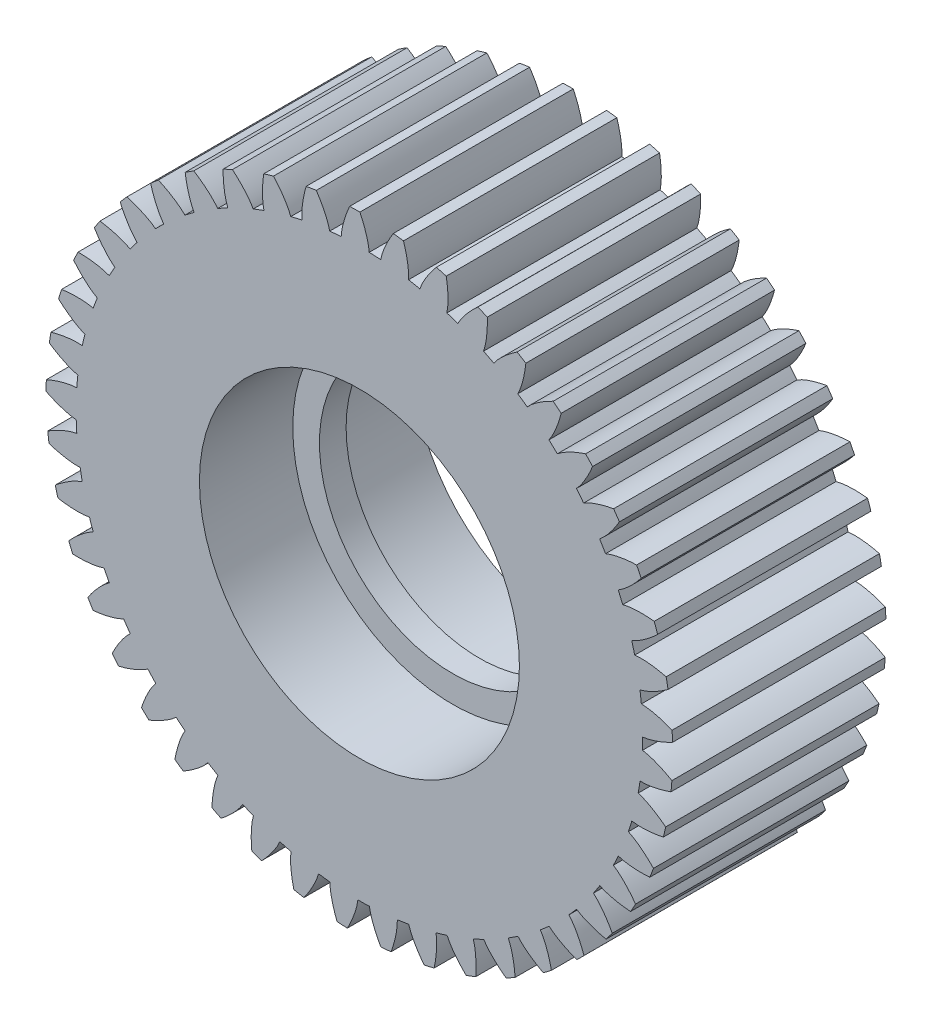
SolidWorks part; units mm, degrees
material "ABS"
ref_plane "Front Plane" through (0, 0, 0) normal (0, 0, 1) x (1, 0, 0)
ref_plane "Top Plane" through (0, 0, 0) normal (0, 1, 0) x (1, 0, 0)
ref_plane "Right Plane" through (0, 0, 0) normal (1, 0, 0) x (0, 0, -1)
sketch "Sketch1" plane through (0, 0, 0) normal (0, 0, 1) x (1, 0, 0)
  circle A0 centre (0, 0) radius 11.75
  dimension "D1" = 23.5
extrude "Boss-Extrude1" add sketch "Sketch1" along normal mid plane 8
sketch "Sketch2" plane through (0, 0, 0) normal (0, 0, 1) x (1, 0, 0)
  line L0 (0, 0) -> (10.5715, 0) construction
  line L1 (0, 0) -> (11.2477, -0.225) construction
  line L2 (0, 0) -> (10.5631, -0.4228) construction
  line L3 (10.5715, 0) -> (10.625, 0)
  line L4 (10.5631, -0.4228) -> (10.6165, -0.4249)
  circle A0 centre (0, 0) radius 11.25 construction
  circle A1 centre (0, 0) radius 10.5715 construction
  circle A2 centre (0, 0) radius 10.625
  circle A3 centre (0, 0) radius 11.75 construction
  circle A4 centre (0, 0) radius 11.75
  spline S0 degree 4 poles (10.5715, 0) (10.5752, 0.0001) (10.5853, 0.0004) (10.6044, 0.0016) (10.6356, 0.0045) (10.6753, 0.0095) (10.7265, 0.0174) (10.7865, 0.0288) (10.8523, 0.0433) (10.9236, 0.0613) (10.9945, 0.0812) (11.0648, 0.1028) (11.1346, 0.126) (11.2188, 0.1559) (11.3192, 0.1944) (11.4357, 0.2433) (11.5668, 0.3032) (11.6991, 0.369) (11.8282, 0.4376) (11.9573, 0.5114) (12.0813, 0.5859) (12.2085, 0.6678) (12.3252, 0.7457) (12.4542, 0.8378) (12.5578, 0.9136) (12.6924, 1.0187) (12.7713, 1.0823) (12.8629, 1.1585) (12.9032, 1.1933) (12.9281, 1.2147) knots 0 0 0 0 0 0.005377 0.015084 0.028532 0.04661 0.064855 0.092111 0.119476 0.146842 0.174209 0.201575 0.228941 0.256307 0.307035 0.361767 0.4165 0.471232 0.525964 0.580697 0.635429 0.690161 0.744894 0.799626 0.854358 0.909091 0.954545 1 1 1 1 1 construction
  spline S1 degree 4 poles (10.5715, 0) (10.5752, 0.0001) (10.5853, 0.0004) (10.6044, 0.0016) (10.6356, 0.0045) (10.6753, 0.0095) (10.7265, 0.0174) (10.7865, 0.0288) (10.8523, 0.0433) (10.9236, 0.0613) (10.9945, 0.0812) (11.0648, 0.1028) (11.1346, 0.126) (11.2188, 0.1559) (11.3192, 0.1944) (11.4357, 0.2433) (11.5668, 0.3032) (11.6991, 0.369) (11.8282, 0.4376) (11.9573, 0.5114) (12.0813, 0.5859) (12.2085, 0.6678) (12.3252, 0.7457) (12.4542, 0.8378) (12.5578, 0.9136) (12.6632, 0.9959) (12.7143, 1.0366) (12.7403, 1.0576) knots 0 0 0 0 0 0.005377 0.015084 0.028532 0.04661 0.064855 0.092111 0.119476 0.146842 0.174209 0.201575 0.228941 0.256307 0.307035 0.361767 0.4165 0.471232 0.525964 0.580697 0.635429 0.690161 0.744894 0.799626 0.854358 0.909091 0.909091 0.909091 0.909091 0.909091
  spline S2 degree 4 poles (10.5631, -0.4228) (10.5667, -0.423) (10.5768, -0.4237) (10.5959, -0.4257) (10.6269, -0.4298) (10.6664, -0.4364) (10.7172, -0.4464) (10.7768, -0.4602) (10.8419, -0.4773) (10.9124, -0.4981) (10.9824, -0.5208) (11.0518, -0.5452) (11.1207, -0.5712) (11.2036, -0.6045) (11.3024, -0.647) (11.4168, -0.7005) (11.5454, -0.7655) (11.675, -0.8366) (11.8012, -0.9103) (11.9273, -0.9892) (12.0482, -1.0686) (12.1721, -1.1555) (12.2856, -1.238) (12.4108, -1.3352) (12.5112, -1.4151) (12.6415, -1.5255) (12.7178, -1.5922) (12.8063, -1.672) (12.8452, -1.7084) (12.8691, -1.7308) knots 0 0 0 0 0 0.005377 0.015084 0.028532 0.04661 0.064855 0.092111 0.119476 0.146842 0.174209 0.201575 0.228941 0.256307 0.307035 0.361767 0.4165 0.471232 0.525964 0.580697 0.635429 0.690161 0.744894 0.799626 0.854358 0.909091 0.954545 1 1 1 1 1 construction
  spline S3 degree 4 poles (10.5631, -0.4228) (10.5667, -0.423) (10.5768, -0.4237) (10.5959, -0.4257) (10.6269, -0.4298) (10.6664, -0.4364) (10.7172, -0.4464) (10.7768, -0.4602) (10.8419, -0.4773) (10.9124, -0.4981) (10.9824, -0.5208) (11.0518, -0.5452) (11.1207, -0.5712) (11.2036, -0.6045) (11.3024, -0.647) (11.4168, -0.7005) (11.5454, -0.7655) (11.675, -0.8366) (11.8012, -0.9103) (11.9273, -0.9892) (12.0482, -1.0686) (12.1721, -1.1555) (12.2856, -1.238) (12.4108, -1.3352) (12.5112, -1.4151) (12.6133, -1.5016) (12.6627, -1.5442) (12.6878, -1.5663) knots 0 0 0 0 0 0.005377 0.015084 0.028532 0.04661 0.064855 0.092111 0.119476 0.146842 0.174209 0.201575 0.228941 0.256307 0.307035 0.361767 0.4165 0.471232 0.525964 0.580697 0.635429 0.690161 0.744894 0.799626 0.854358 0.909091 0.909091 0.909091 0.909091 0.909091
  dimension "D1" = 22.5
  dimension "D2" = 21.1431
  dimension "D3" = 21.25
  dimension "D4" = 1.146
  dimension "D5" = 1.146
extrude "Cut-Extrude1" cut sketch "Sketch2" against normal through all both and the other way through all contours A2 S3 A4 S1 region at (11.2841, -0.2257, 0)
pattern_circular "CirPattern2" count 45 over 360 about axis through (0, 0, 4) along (0, 0, -1) of "Cut-Extrude1"
sketch "Sketch3" plane through (0, 0, 4) normal (0, 0, 1) x (1, 0, 0)
  circle A0 centre (0, 0) radius 6
  dimension "D1" = 12
extrude "Cut-Extrude2" cut sketch "Sketch3" against normal blind 3.5
sketch "Sketch4" plane through (0, 0, 0.5) normal (0, 0, 1) x (1, 0, 0)
  circle A0 centre (0, 0) radius 5
  dimension "D1" = 10
extrude "Cut-Extrude3" cut sketch "Sketch4" against normal through all
mirror "Mirror1" about plane through (0, 0, 0) normal (0, 0, 1) of "Cut-Extrude2"
equation "\"Np\" = 45"
equation "\"module\" = 0.5"
equation "\"pressure angle\" = 20.0"
equation "\"h_a\" = 0.5"
equation "\"h_b\" = 0.625"
equation "\"clr_tip_root\" = 0.125"
equation "\"dp_p\" = 22.5"
equation "\"db_p\" = 21.14308396768294"
equation "\"D1@Sketch1\"= \"dp_p\" + 2*\"h_a\" "
equation "\"fw_p\" = 8.0"
equation "\"D1@Boss-Extrude1\"=\"fw_p\""
equation "\"D1@Sketch2\"=\"dp_p\""
equation "\"D2@Sketch2\"= \"db_p\""
equation "\"D3@Sketch2\"=\"dp_p\"- 2*\"h_b\""
equation "\"alpha_p\" = 0.8539582918412307"
equation "\"D4@Sketch2\"= 360 / ( 4 * \"Np\" ) - \"alpha_p\""
equation "\"beta_p\" = 2.2920834163175385"
equation "\"D5@Sketch2\"= 360 / ( 4 * \"Np\" ) - \"alpha_p\""
equation "\"D1@CirPattern2\"=\"Np\""
equation "\"Nr\" = 123"
equation "\"pressure_angle\" = 20.0"
equation "\"h_f\" = 0.625"
equation "\"dp_r\" = 61.5"
equation "\"db_r\" = 57.79109617833337"
equation "\"fw_r\" = 8.0"
equation "\"alpha_r\" = 0.8539582918412414"
equation "\"beta_r\" = 3.171331217828824"
equation "\"bearing_ID\" = 50"
equation "\"bearing_OD\" = 65"
equation "\"bearing_height\" = 7"
equation "\"clearance_planet\" = 1.5"
equation "\"case_dist\" = 6.0"
equation "\"Motor_case_OD_max\" = 96.5"
equation "\"case_mounting_PCD\" = 89.0"
equation "\"bearing mount thickness\" = 8"
equation "\"case_mounting_hole_dia\" = 3"
equation "\"output_mounting_PCD\" = 73"
equation "\"output_mounting_hole_dia\" = 4"
equation "\"clearance_case_mount_holes_shell_thickness\" = 1"
equation "\"motor_case_OD_base\" = 87.0"
equation "\"sec_carrier_thickness\" = 5"
equation "\"sun_coupler_hub_thickness\" = 4"
equation "\"clearance_sun_coupler_sec_carrier\" = 1.5"
equation "\"clearance_motor_and_case\" = 5"
equation "\"motor_OD\" = 72"
equation "\"Motor_case_thickness\" = 2.5"
equation "\"Motor_case_ID\" = 82"
equation "\"case_mounting_hole_shift\" = 1.0"
equation "\"output_mounting_nut_wrench_size\" = 7"
equation "\"output_mounting_nut_thickness\" = 3.2"
equation "\"case_mounting_hole_allen_socket_dia\" = 5.5"
equation "\"output_mounting_nut_depth\" = 3"
equation "\"case_mounting_bolt_depth\" = 4.5"
equation "\"Ns\" = 33"
equation "\"ring_radial_thickness\" = 5"
equation "\"ring_OD\" = 71.5"
equation "\"ring_to_chamfer_clearance\" = 2"
equation "\"Motor_case_OD_base_to_chamfer\" = 5"
equation "\"pattern_offset_from_motor_case_OD_base\" = 3"
equation "\"pattern_bulge_dia\" = 3"
equation "\"pattern_num_bulge\" = 18"
equation "\"pattern_depth\" = 2"
equation "\"motor_height\" = 27"
equation "\"case_mounting_wrench_size\" = 5.5"
equation "\"case_mounting_nut_clearance\" = 2"
equation "\"base_plate_thickness\" = 4"
equation "\"case_mounting_nut_thickness\" = 2.4"
equation "\"case_mounting_surface_height\" = 4"
equation "\"motor_mount_hole_PCD\" = 32"
equation "\"motor_mount_hole_dia\" = 4"
equation "\"motor_mount_hole_num\" = 4"
equation "\"central_hole_offset_from_motor_mount_PCD\" = 5"
equation "\"wire_slot_dist_from_center\" = 30"
equation "\"wire_slot_length\" = 10"
equation "\"wire_slot_radius\" = 2.5"
equation "\"driver_upper_holes_dist_from_center\" = 23"
equation "\"driver_lower_holes_dist_from_center\" = 15"
equation "\"driver_side_holes_dist_from_center\" = 20"
equation "\"driver_mount_holes_dia\" = 2.5"
equation "\"driver_mount_inserts_OD\" = 3.5"
equation "\"driver_mount_thickness\" = 1.5"
equation "\"driver_mount_height\" = 4"
equation "\"air_flow_hole_offset\" = 3"
equation "\"num_planet\" = 3"
equation "\"planet_pin_bolt_dia\" = 5"
equation "\"planet_pin_socket_head_dia\" = 8.5"
equation "\"carrier_PCD\" = 39.0"
equation "\"planet_shaft_dia\" = 8"
equation "\"planet_shaft_step_offset\" = 1"
equation "\"carrier_trapezoidal_support_sun_offset\" = 5"
equation "\"carrier_trapezoidal_support_hole_PCD_offset_bearing_ID\" = 4"
equation "\"carrier_trapezoidal_support_hole_dia\" = 3"
equation "\"carrier_trapezoidal_support_hole_socket_head_dia\" = 5.5"
equation "\"carrier_bearing_step_width\" = 1.5"
equation "\"standard_clearance_1_5mm\" = 1.5"
equation "\"standard_fillet_1_5mm\" = 1.5"
equation "\"sun_shaft_bearing_OD\" = 16"
equation "\"sun_shaft_bearing_width\" = 5"
equation "\"standard_bearing_insertion_chamfer\" = 0.5"
equation "\"carrier_trapezoidal_support_hole_wrench_size\" = 5.5"
equation "\"planet_pin_bolt_wrench_size\" = 8"
equation "\"planet_bearing_OD\" = 12"
equation "\"planet_bearing_width\" = 3.5"
equation "\"planet_bore\" = 10"
equation "\"D1@Cut-Extrude2\"= \"planet_bearing_width\""
equation "\"D1@Sketch4\"=\"planet_bore\""
equation "\"motor_output_hole_PCD\" = 22"
equation "\"motor_output_hole_dia\" = 3"
equation "\"motor_output_hole_num\" = 4"
equation "\"dp_s\" = 16.5"
equation "\"db_s\" = 15.50492824296749"
equation "\"fw_s_calc\" = 5.95406185839039"
equation "\"alpha_s\" = 0.8539582918412449"
equation "\"beta_s\" = 3.7466288708629643"
equation "\"sun_shaft_bearing_ID\" = 8"
equation "\"sun_hub_dia\" = 31.0"
equation "\"sun_central_bolt_dia\" = 5"
equation "\"sun_central_bolt_socket_head_dia\" = 8.5"
equation "\"fw_s_used\" = 16.0"
equation "\"motor_output_hole_CSK_OD\" = 6"
equation "\"motor_output_hole_CSK_head_height\" = 1.5"
equation "\"bearing_retainer_thickness\" = 2"
equation "\"D4@Sketch4\"=\"carrier_trapezoidal_support_sun_offset\""
equation "\"D2@Sketch5\"=\"carrier_trapezoidal_support_hole_dia\""
equation "\"D1@Sketch6\"=\"carrier_trapezoidal_support_hole_socket_head_dia\""
equation "\"D1@Cut-Extrude3\"=\"planet_pin_bolt_dia\""
equation "\"D1@Sketch7\"=\"planet_pin_socket_head_dia\""
equation "\"D1@Sketch9\"=\"sun_shaft_bearing_OD\""
equation "\"D1@Sketch10\"=\"standard_clearance_1_5mm\""
equation "\"D1@Sketch3\"= \"planet_bearing_OD\""
equation "\"Ns1\" = 33"
equation "\"Np1\" = 45"
equation "\"Nr1\" = 123"
equation "\"module1\" = 0.5"
equation "\"bearing1_ID\" = 50"
equation "\"bearing1_OD\" = 65"
equation "\"bearing1_height1\" = 7"
equation "\"bearing mount thickness1\" = 8"
equation "\"output_mounting_PCD1\" = 73"
equation "\"num_planet1\" = 3"
equation "\"stg1_stg2_mounting_pattern_width\" = 12"
equation "\"stg1_stg2_allen_socket_head_dia\" = 7.0"
equation "\"stg1_stg2_mounting_hole_dia\" = 4"
equation "\"stg1_stg2_mounting_extra_width\" = 5.25"
equation "\"tight_clearance_3DP\" = 0.4"
equation "\"loose_clearance_3DP\" = 0.8"
